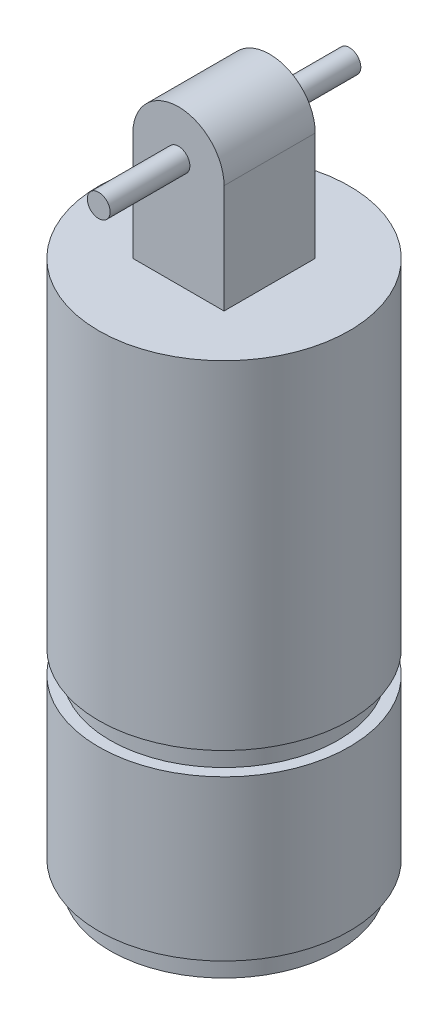
SolidWorks part; units mm, degrees
ref_plane "Front Plane" through (0, 0, 0) normal (0, 0, 1) x (1, 0, 0)
ref_plane "Top Plane" through (0, 0, 0) normal (0, 1, 0) x (1, 0, 0)
ref_plane "Right Plane" through (0, 0, 0) normal (1, 0, 0) x (0, 0, -1)
ref_plane "end plane" through (0, 23.8125, 0) normal (0, 1, 0) x (1, 0, 0)
sketch "Sketch4" plane through (0, 0, 0) normal (0, 1, 0) x (1, 0, 0)
  circle A0 centre (0, 0) radius 5
  dimension "D1" = 10
extrude "Boss-Extrude1" add sketch "Sketch4" along normal blind 9
ref_plane "Plane2" through (0, 4.5, 0) normal (0, 1, 0) x (1, 0, 0)
sketch "Sketch5" plane through (0, 4.5, 0) normal (0, 1, 0) x (1, 0, 0)
  circle A0 centre (0, 0) radius 5.5
  dimension "D1" = 11
extrude "Boss-Extrude2" add sketch "Sketch5" along normal mid plane 7
sketch "Sketch6" plane through (0, 9, 0) normal (0, 1, 0) x (1, 0, 0)
  circle A0 centre (0, 0) radius 5.5
  dimension "D1" = 11
extrude "Boss-Extrude3" add sketch "Sketch6" along normal up to surface (14.8125 mm away) up to plane "end plane"
sketch "Sketch7" plane through (0, 0, 0) normal (0, -1, 0) x (1, 0, 0)
  circle A0 centre (0, 0) radius 4
  dimension "D1" = 8
extrude "Cut-Extrude1" cut sketch "Sketch7" against normal blind 7
sketch "Sketch8" plane through (0, 0, 0) normal (0, 0, 1) x (1, 0, 0)
  line L0 (-2, 23.8125) -> (2, 23.8125)
  line L1 (5.5, 23.8125) -> (-5.5, 23.8125) construction
  line L2 (2, 23.8125) -> (2, 28.575)
  line L3 (-2, 28.575) -> (-2, 23.8125)
  line L4 (0, 0) -> (0, 21.6121) construction
  line L5 (-5, 0) -> (5, 0) construction
  arc A0 (2, 28.575) -> (-2, 28.575) centre (0, 28.575) ccw
  dimension "D1" = 4.7625
  dimension "D2" = 4
extrude "Boss-Extrude4" add sketch "Sketch8" along normal mid plane 4
sketch "Sketch10" plane through (0, 0, 0) normal (0, 0, 1) x (1, 0, 0)
  circle A0 centre (0, 28.575) radius 0.5
  dimension "D1" = 1
extrude "Boss-Extrude5" add sketch "Sketch10" along normal through all and the other way through all
